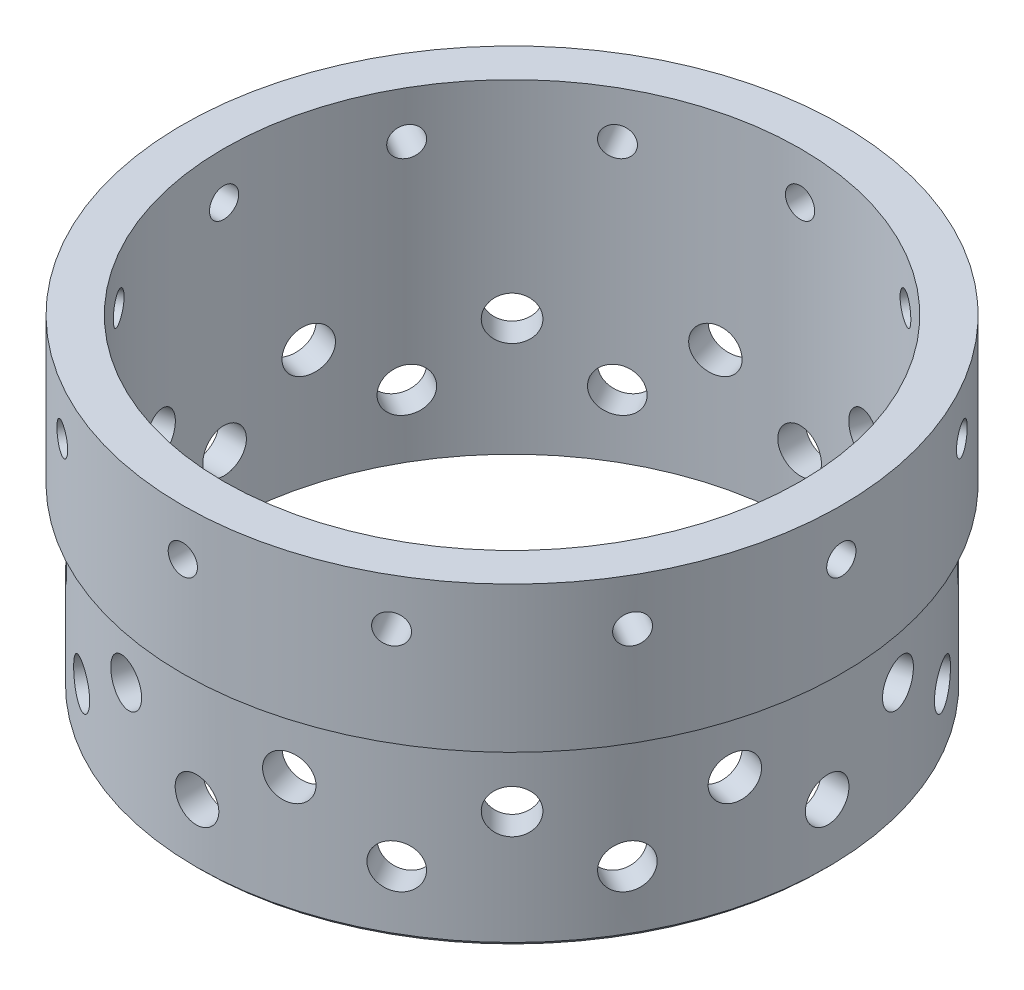
SolidWorks part; units mm, degrees
material "6061-T6 (SS)"
ref_plane "Front Plane" through (0, 0, 0) normal (0, 0, 1) x (1, 0, 0)
ref_plane "Top Plane" through (0, 0, 0) normal (0, 1, 0) x (1, 0, 0)
ref_plane "Right Plane" through (0, 0, 0) normal (1, 0, 0) x (0, 0, -1)
sketch "Sketch1" plane through (0, 0, 0) normal (0, 1, 0) x (1, 0, 0)
  circle A0 centre (0, 0) radius 66.5988
  circle A1 centre (0, 0) radius 76.1238
  circle A2 centre (0, 0) radius 72.9488
  dimension "D1" = 152.2476
  dimension "D2" = 3.175
  dimension "D3" = 6.35
  dimension "D4" = 9.525
  dimension "D5" = 145.8976
extrude "Boss-Extrude1" add sketch "Sketch1" along normal blind 12.7 contours A2 A0 | A1 A2 region at (-73.9707, 0, 0) region at (-70.8855, 0, 0)
extrude "Boss-Extrude2" add sketch "Sketch1<3>" against normal blind 41.275 contours A2 A0 region at (-70.8855, 0, 0)
sketch "Sketch1<3>" plane through (0, 0, 0) normal (0, 1, 0) x (1, 0, 0) same geometry as "Sketch1"
extrude "Boss-Extrude3" add sketch "Sketch1<4>" along normal blind 33.655 contours A2 A0 | A1 A2 region at (-73.9707, 0, 0) region at (-70.8855, 0, 0)
sketch "Sketch1<4>" plane through (0, 0, 0) normal (0, 1, 0) x (1, 0, 0) same geometry as "Sketch1"
chamfer "Chamfer1" distance 1 angle 45 1 edges at (0, -41.275, 72.9488)
sketch "Sketch2" plane through (0, 0, 0) normal (0, 0, 1) x (1, 0, 0)
  line L0 (0, 0) -> (0, 22.86) construction
  line L1 (0, 0) -> (0, -26.797) construction
  line L2 (-71.9488, -41.275) -> (71.9488, -41.275) construction
  line L4 (76.1238, 33.655) -> (-76.1238, 33.655) construction
  circle A0 centre (0, 22.86) radius 3.3782
  circle A1 centre (0, -26.797) radius 5.0419
  dimension "D1" = 6.7564
  dimension "D2" = 10.0838
  dimension "D3" = 26.797
  dimension "D5" = 14.478
  dimension "D4" = 10.795
extrude "Cut-Extrude1" cut sketch "Sketch2" against normal through all contours A1 region at (0, -26.797, 0)
ref_plane "Plane1" through (-19.7023, 0, 73.5299) normal (-0.2588, 0, 0.9659) x (0, -1, 0)
sketch "Sketch3" plane through (-19.7023, 0, 73.5299) normal (-0.2588, 0, 0.9659) x (0, -1, 0)
  line L0 (14.097, 0) -> (0, 0) construction
  line L1 (41.275, -71.9488) -> (41.275, 71.9488) construction
  circle A0 centre (14.097, 0) radius 5.0419
  dimension "D1" = 10.0838
  dimension "D2" = 14.097
  dimension "D3" = 27.178
extrude "Cut-Extrude2" cut sketch "Sketch3" against normal blind 38.1
pattern_circular "CirPattern2" count 12 over 360 about axis through (0, 12.7, 0) along (0, -1, 0) of "Cut-Extrude2", "Cut-Extrude1" reverse direction yes
extrude "Cut-Extrude3" cut sketch "Sketch2<3>" against normal through all contours A0
sketch "Sketch2<3>" plane through (0, 0, 0) normal (0, 0, 1) x (1, 0, 0) same geometry as "Sketch2"
pattern_circular "CirPattern3" count 12 over 360 about axis through (0, 12.7, 0) along (0, -1, 0) of "Cut-Extrude3"
fillet "Fillet1" radius 0.4064 1 edges at (0, 0, 72.9488)
equation "\"holeDia\"= 0.397in"
equation "\"D2@Sketch2\"=\"holeDia\""
equation "\"numHoles\"=12"
equation "\"D1@Plane1\"=180/\"numHoles\""
equation "\"D1@Sketch3\"=\"holeDia\""
equation "\"D1@CirPattern2\"=\"numHoles\""
